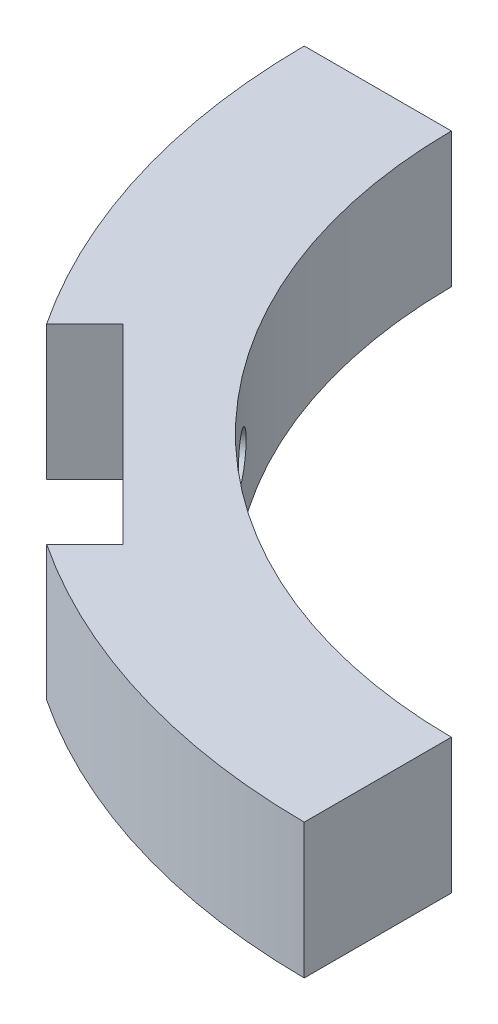
SolidWorks part; units mm, degrees
material "6061-T6 (SS)"
ref_plane "Front Plane" through (0, 0, 0) normal (0, 0, 1) x (1, 0, 0)
ref_plane "Top Plane" through (0, 0, 0) normal (0, 1, 0) x (1, 0, 0)
ref_plane "Right Plane" through (0, 0, 0) normal (1, 0, 0) x (0, 0, -1)
sketch "Sketch1" plane through (0, 0, 0) normal (0, 1, 0) x (1, 0, 0)
  line L0 (0, 0) -> (-24.5, 0) construction
  line L1 (0, 0) -> (0, -24.5) construction
  line L2 (-19.5497, -0.1) -> (-24.9998, -0.1)
  line L3 (-0.1, -19.5497) -> (-0.1, -24.9998)
  line L4 (-0.1, -0.1) -> (-24.5, -0.1) construction
  line L5 (-0.1, -0.1) -> (-0.1, -24.5) construction
  arc A0 (-19.5497, -0.1) -> (-0.1, -19.5497) centre (0, 0) ccw
  arc A1 (-24.9998, -0.1) -> (-0.1, -24.9998) centre (0, 0) ccw
  dimension "D1" = 39.1
  dimension "D2" = 50
  dimension "D3" = 0.1
extrude "Boss-Extrude1" add sketch "Sketch1" along normal mid plane 5
sketch "Sketch2" plane through (0, 2.5, 0) normal (0, 1, 0) x (1, 0, 0)
  line L0 (-17.6777, -17.6777) -> (0, 0) construction
  line L1 (-21.2132, -14.1421) -> (-14.1421, -21.2132)
  line L5 (-21.2132, -14.1421) -> (-19.4454, -12.3744)
  line L6 (-19.4454, -12.3744) -> (-12.3744, -19.4454)
  line L7 (-12.3744, -19.4454) -> (-14.1421, -21.2132)
  arc A0 (-24.9998, -0.1) -> (-0.1, -24.9998) centre (0, 0) ccw construction
  point P9 (-17.6777, -17.6777)
  dimension "D1" = 2.5
  dimension "D2" = 10
extrude "Cut-Extrude1" cut sketch "Sketch2" against normal through all
sketch "Sketch3" plane through (-15.9099, 0, 15.9099) normal (-0.7071, 0, 0.7071) x (0.7071, 0, 0.7071)
  line L0 (-5, 0) -> (5, 0) construction
  line L1 (-5, -2.5) -> (-5, 2.5) construction
  line L2 (5, 2.5) -> (5, -2.5) construction
  line L3 (0, 0) -> (0, 2.5) construction
  line L4 (5, 2.5) -> (-5, 2.5) construction
  point P6 (-2.5, 0)
  point P12 (2.5, 0)
  dimension "D1" = 2.5
hole_wizard "Tap Drill for M2x0.4 Tap1" positions "3DSketch1" profile "Sketch4" hole size "M2x0.4" standard "ANSI Metric" end condition through all
sketch3d "3DSketch1"
  point P0 (-17.6777, 0, 14.1421)
  point P3 (-14.1421, 0, 17.6777)
sketch "Sketch4" plane through (-17.6777, 0, 14.1421) normal (0, 1, 0) x (0.7071, 0, 0.7071)
  line L0 (0, 0) -> (0, 22.3586)
  line L1 (0, 22.3586) -> (0.8, 22.3586)
  line L2 (0.8, 22.3586) -> (0.8, 0)
  line L5 (0.8, 0) -> (0, 0)
  line L11 (0, -6.35) -> (0, 107.95) construction
  dimension "Thru Hole Dia." = 1.6
  dimension "Thru Hole Depth" = 22.3586
thread "Thread1" pitch 0.4 method extrude profile "Thread Profile1" start angle 0, offset 0, length 0.8, pitch 0.4, diameter 1.6
ref_plane "Plane1" through (-18.2434, 0, 13.5765) normal (0, -1, 0) x (-0.7071, 0, -0.7071)
sketch "Thread Profile1" plane through (-18.2434, 0, 13.5765) normal (0, -1, 0) x (-0.7071, 0, -0.7071)
  line L0 (0, 0) -> (0, 0.4) construction
  line L11 (0, 0) -> (0, 0.35)
  line L12 (0, 0.35) -> (-0.2165, 0.225)
  line L13 (-0.2165, 0.225) -> (-0.2165, 0.125)
  line L15 (-0.2165, 0.125) -> (0, 0)
  line L17 (-0.2165, 0.175) -> (0, 0.175) construction
  point P2 (0, 0)
  dimension "Pitch" = 0.4
  dimension "Profile_Angle" = 60
  dimension "Profile_Land" = 0.1
  dimension "Profile_Height" = 0.2165
thread "Thread2" pitch 0.4 method extrude profile "Thread Profile2" start angle 0, offset 0, length 0.8, pitch 0.4, diameter 1.6
ref_plane "Plane2" through (-14.7078, 0, 17.112) normal (0, -1, 0) x (-0.7071, 0, -0.7071)
sketch "Thread Profile2" plane through (-14.7078, 0, 17.112) normal (0, -1, 0) x (-0.7071, 0, -0.7071)
  line L0 (0, 0) -> (0, 0.4) construction
  line L11 (0, 0) -> (0, 0.35)
  line L12 (0, 0.35) -> (-0.2165, 0.225)
  line L13 (-0.2165, 0.225) -> (-0.2165, 0.125)
  line L15 (-0.2165, 0.125) -> (0, 0)
  line L17 (-0.2165, 0.175) -> (0, 0.175) construction
  point P2 (0, 0)
  dimension "Pitch" = 0.4
  dimension "Profile_Angle" = 60
  dimension "Profile_Land" = 0.1
  dimension "Profile_Height" = 0.2165
